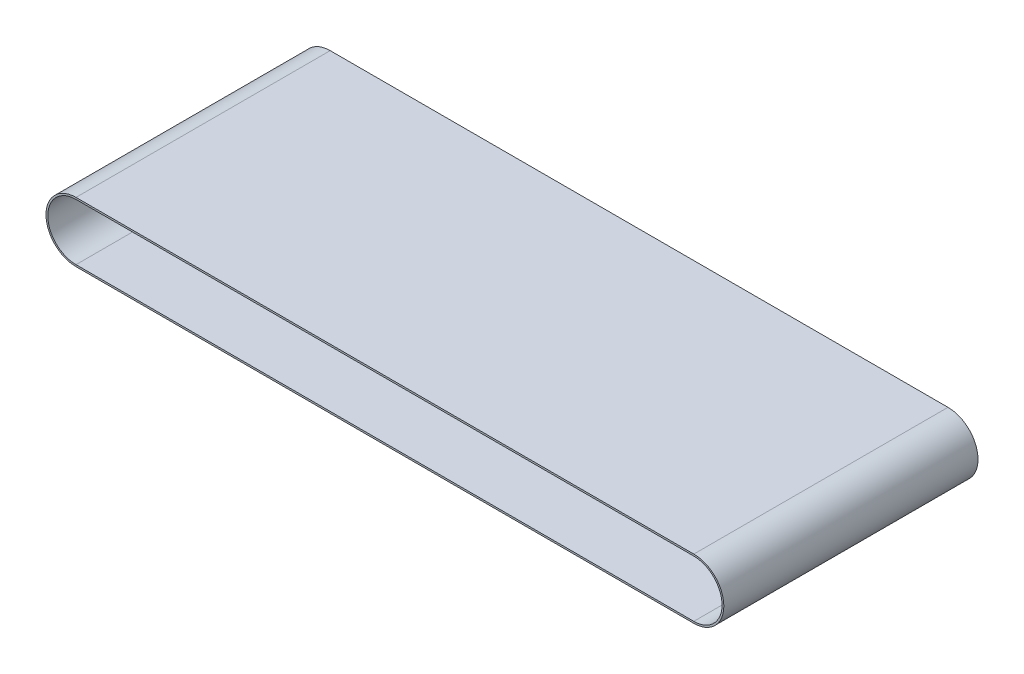
SolidWorks part; units mm, degrees
material "Silicon Rubber"
ref_plane "Front Plane" through (0, 0, 0) normal (0, 0, 1) x (1, 0, 0)
ref_plane "Top Plane" through (0, 0, 0) normal (0, 1, 0) x (1, 0, 0)
ref_plane "Right Plane" through (0, 0, 0) normal (1, 0, 0) x (0, 0, -1)
sketch "Sketch1" plane through (0, 0, 0) normal (0, 0, 1) x (1, 0, 0)
  line L0 (0, 26.9875) -> (555.625, 26.9875)
  line L1 (0, -26.9875) -> (555.625, -26.9875)
  arc A0 (0, 26.9875) -> (0, -26.9875) centre (0, 0) ccw
  arc A1 (555.625, -26.9875) -> (555.625, 26.9875) centre (555.625, 0) ccw
extrude "Boss-Extrude1" add sketch "Sketch1" against normal mid plane 228.6
sketch "Sketch3" plane through (0, 0, 114.3) normal (0, 0, 1) x (1, 0, 0)
  line L0 (0, 25.4) -> (555.625, 25.4)
  line L1 (0, -25.4) -> (555.625, -25.4)
  arc A0 (0, 25.4) -> (0, -25.4) centre (0, 0) ccw
  arc A1 (555.625, -25.4) -> (555.625, 25.4) centre (555.625, 0) ccw
extrude "Cut-Extrude1" cut sketch "Sketch3" against normal through all contours L0 A1 L1 A0
ref_plane "Plane1" through (0, -96.8375, 0) normal (0, -1, 0) x (-1, 0, 0)
sketch "Sketch6" plane through (0, 0, 0) normal (0, 0, 1) x (1, 0, 0)
  line L0 (0, -26.9875) -> (555.625, -26.9875) construction
  line L1 (555.625, 26.9875) -> (0, 26.9875) construction
  line L2 (0, -26.9875) -> (555.625, -26.9875)
  line L3 (555.625, 26.9875) -> (0, 26.9875)
  arc A0 (555.625, -26.9875) -> (555.625, 26.9875) centre (555.625, 0) ccw construction
  arc A1 (0, 26.9875) -> (0, -26.9875) centre (0, 0) ccw construction
  arc A2 (555.625, -26.9875) -> (555.625, 26.9875) centre (555.625, 0) ccw
  arc A3 (0, 26.9875) -> (0, -26.9875) centre (0, 0) ccw
